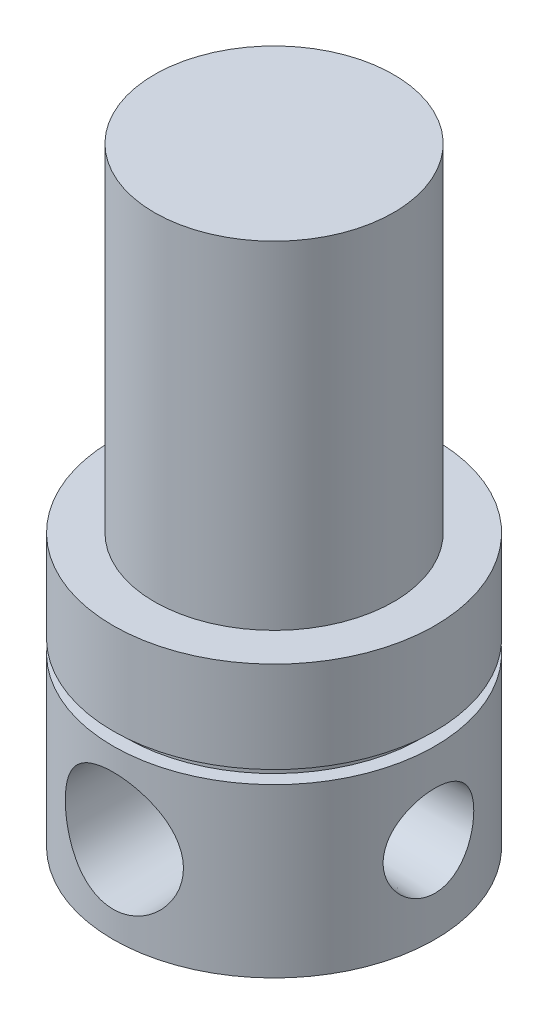
SolidWorks part; units mm, degrees
material "Alloy Steel (SS)"
ref_plane "Front Plane" through (0, 0, 0) normal (0, 0, 1) x (1, 0, 0)
ref_plane "Top Plane" through (0, 0, 0) normal (0, 1, 0) x (1, 0, 0)
ref_plane "Right Plane" through (0, 0, 0) normal (1, 0, 0) x (0, 0, -1)
sketch "Sketch1" plane through (0, 0, 0) normal (1, 0, 0) x (0, 0, -1)
  line L0 (0, 33.6506) -> (0, -33.6506) construction
  line L1 (0, 50.038) -> (13.97, 50.038)
  line L2 (13.97, 50.038) -> (13.97, 10.668)
  line L3 (13.97, 10.668) -> (18.796, 10.668)
  line L4 (18.796, 10.668) -> (18.796, 0)
  line L5 (18.796, 0) -> (17.2085, 0)
  line L6 (17.2085, 0) -> (17.2085, -1.524)
  line L7 (17.2085, -1.524) -> (18.796, -1.524)
  line L8 (18.796, -1.524) -> (18.796, -21.082)
  line L9 (18.796, -21.082) -> (0, -21.082)
  line L10 (0, -21.082) -> (0, 50.038)
  point P2 (0, 0)
  dimension "D1" = 13.97
  dimension "D2" = 18.796
  dimension "D3" = 71.12
  dimension "D4" = 39.37
  dimension "D5" = 1.5875
  dimension "D6" = 19.558
  dimension "D7" = 10.668
revolve "Revolve1" add sketch "Sketch1" angle 360 about L0
ref_plane "Plane1" through (0, 0, 0) normal (0, -1, 0) x (-1, 0, 0)
split "Split1" trim tools "Plane1" bodies to split 101 resulting bodies 102 103
ref_plane "Plane2" through (18.796, 0, 0) normal (1, 0, 0) x (0, 0, -1)
hole_wizard "1/8 NPT Tapped Hole1" positions "Sketch2" profile "Sketch3" size "1/8" standard "ANSI Inch"
sketch "Sketch2" plane through (18.796, 0, 0) normal (1, 0, 0) x (0, 0, -1)
  line L0 (0, -21.082) -> (0, -11.082) construction
  line L1 (-18.796, -21.082) -> (18.796, -21.082) construction
  point P0 (0, -11.082)
  dimension "D1" = 10
sketch "Sketch3" plane through (18.796, -11.082, 0) normal (0, 1, 0) x (0, 0, -1)
  line L0 (0, 0) -> (0, 16.5035)
  line L1 (4.2164, 13.97) -> (0, 16.5035)
  line L2 (-4.2164, 13.97) -> (0, 16.5035) construction
  line L3 (4.2164, 13.97) -> (4.2164, 12.7)
  line L4 (4.2164, 12.7) -> (4.9362, 12.7)
  line L5 (4.9362, 12.7) -> (5.3164, 0)
  line L6 (-4.9362, 12.7) -> (-5.3164, 0) construction
  line L7 (5.3164, 0) -> (0, 0)
  line L8 (0, -6.35) -> (0, 107.95) construction
  line L11 (-4.2164, 12.7) -> (-4.9362, 12.7) construction
  dimension "Tap Drill Dia." = 8.4328
  dimension "Tap Drill Depth" = 13.97
  dimension "Thread Dia." = 10.6329
  dimension "Thread Angle" = 3.43
  dimension "Thread Depth" = 12.7
  dimension "Drill Angle" = 118
mirror "Mirror1" about plane through (0, 0, 0) normal (1, 0, 0) of "1/8 NPT Tapped Hole1"
ref_plane "Plane3" through (0, 0, -18.796) normal (0, 0, -1) x (-1, 0, 0)
hole_wizard "1/4 NPT Tapped Hole1" positions "Sketch4" profile "Sketch5" size "1/4" standard "ANSI Inch"
sketch "Sketch4" plane through (0, 0, -18.796) normal (0, 0, -1) x (-1, 0, 0)
  line L0 (0, -21.082) -> (0, -11.082) construction
  line L1 (-18.796, -21.082) -> (18.796, -21.082) construction
  point P0 (0, -11.082)
  dimension "D1" = 10
sketch "Sketch5" plane through (0, -11.082, -18.796) normal (1, 0, 0) x (0, 1, 0)
  line L0 (0, 0) -> (0, 17.3123)
  line L1 (5.5626, 13.97) -> (0, 17.3123)
  line L2 (-5.5626, 13.97) -> (0, 17.3123) construction
  line L3 (5.5626, 13.97) -> (5.5626, 12.7)
  line L4 (5.5626, 12.7) -> (6.558, 12.7)
  line L5 (6.558, 12.7) -> (6.9382, 0)
  line L6 (-6.558, 12.7) -> (-6.9382, 0) construction
  line L7 (6.9382, 0) -> (0, 0)
  line L8 (0, -6.35) -> (0, 107.95) construction
  line L11 (-5.5626, 12.7) -> (-6.558, 12.7) construction
  dimension "Tap Drill Dia." = 11.1252
  dimension "Tap Drill Depth" = 13.97
  dimension "Thread Dia." = 13.8765
  dimension "Thread Angle" = 3.43
  dimension "Thread Depth" = 12.7
  dimension "Drill Angle" = 118
mirror "Mirror2" about plane through (0, 0, 0) normal (0, 0, 1) of "1/4 NPT Tapped Hole1"
ref_axis "Axis1" through (0, -21.082, 0) along (0, 1, 0)
